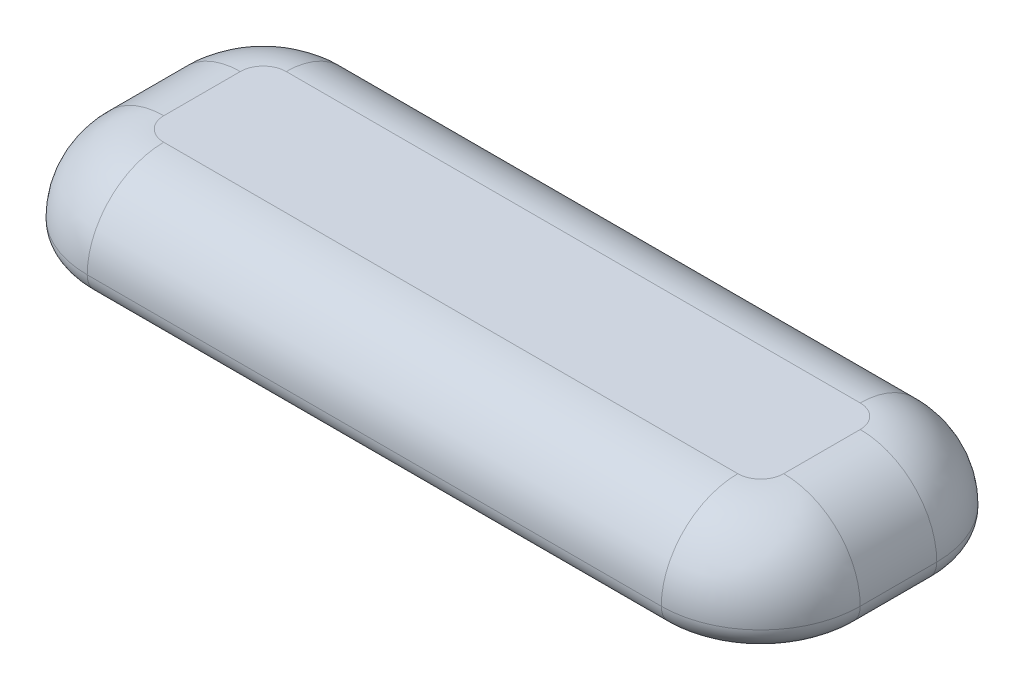
SolidWorks part; units mm, degrees
ref_plane "前视基准面" through (0, 0, 0) normal (0, 0, 1) x (1, 0, 0)
ref_plane "上视基准面" through (0, 0, 0) normal (0, 1, 0) x (1, 0, 0)
ref_plane "右视基准面" through (0, 0, 0) normal (1, 0, 0) x (0, 0, -1)
sketch "草图1" plane through (0, 0, 0) normal (0, 1, 0) x (1, 0, 0)
  line L1 (-37.5, 15) -> (37.5, 15)
  line L2 (-47.5, 5) -> (-47.5, -5)
  line L3 (-37.5, -15) -> (37.5, -15)
  line L4 (47.5, 5) -> (47.5, -5)
  line L5 (0, -15) -> (0, 15) construction
  line L6 (-47.5, 0) -> (47.5, 0) construction
  arc A0 (-47.5, -5) -> (-37.5, -15) centre (-37.5, -5) ccw
  arc A1 (-47.5, 5) -> (-37.5, 15) centre (-37.5, 5) cw
  arc A2 (37.5, 15) -> (47.5, 5) centre (37.5, 5) cw
  arc A3 (47.5, -5) -> (37.5, -15) centre (37.5, -5) cw
  point P0 (0, 0)
  point P8 (-47.5, 15)
  point P11 (47.5, 15)
  point P15 (47.5, -15)
  dimension "D3" = 10
  dimension "D1" = 95
  dimension "D2" = 30
extrude "凸台-拉伸1" add sketch "草图1" along normal blind 10
shell "抽壳2" thickness 3 removed face at (0, 0, 0) outward yes
fillet "圆角3" radius 10 8 edges at (46.6924, 13, -14.1924) (50.5, 13, 0) (46.6924, 13, 14.1924) (0, 13, 18) (-46.6924, 13, 14.1924) (-50.5, 13, 0) (-46.6924, 13, -14.1924) (0, 13, -18)
fillet "圆角4" radius 3 8 edges at (50.5, 0, 0) (46.6924, 0, 14.1924) (0, 0, 18) (-46.6924, 0, 14.1924) (-50.5, 0, 0) (-46.6924, 0, -14.1924) (0, 0, -18) (46.6924, 0, -14.1924)
ref_plane "基准面1" through (0, 10, 0) normal (0, -1, 0) x (-1, 0, 0)
sketch "草图2" plane through (0, 10, 0) normal (0, -1, 0) x (-1, 0, 0)
  line L0 (0, 0) -> (36.7, 0) construction
  line L1 (0, 0) -> (0, 6.5357) construction
  line L2 (34.625, 0.575) -> (38.775, 0.575)
  line L3 (34.625, 0.575) -> (34.625, -0.575)
  line L4 (34.625, -0.575) -> (38.775, -0.575)
  line L5 (38.775, 0.575) -> (38.775, -0.575)
  line L6 (36.7, -0.575) -> (36.7, 0.575) construction
  line L7 (34.625, 0) -> (38.775, 0) construction
  line L8 (36.125, 2.075) -> (37.275, 2.075)
  line L9 (36.125, 2.075) -> (36.125, -2.075)
  line L10 (36.125, -2.075) -> (37.275, -2.075)
  line L11 (37.275, 2.075) -> (37.275, -2.075)
  line L12 (36.7, -2.075) -> (36.7, 2.075) construction
  line L13 (36.125, 0) -> (37.275, 0) construction
  line L14 (-36.125, 0) -> (-37.275, 0) construction
  line L15 (-36.7, -2.075) -> (-36.7, 2.075) construction
  line L16 (-34.625, 0) -> (-38.775, 0) construction
  line L17 (-36.7, -0.575) -> (-36.7, 0.575) construction
  line L18 (-37.275, 2.075) -> (-37.275, -2.075)
  line L19 (-36.125, -2.075) -> (-37.275, -2.075)
  line L20 (-36.125, 2.075) -> (-36.125, -2.075)
  line L21 (-36.125, 2.075) -> (-37.275, 2.075)
  line L22 (-38.775, 0.575) -> (-38.775, -0.575)
  line L23 (-34.625, -0.575) -> (-38.775, -0.575)
  line L24 (-34.625, 0.575) -> (-34.625, -0.575)
  line L25 (-34.625, 0.575) -> (-38.775, 0.575)
  circle A0 centre (36.7, 0) radius 2.675
  circle A1 centre (-36.7, 0) radius 2.675
  dimension "D2" = 5.35
  dimension "D1" = 36.7
  dimension "D3" = 4.15
  dimension "D4" = 1.15
  dimension "D5" = 4.15
  dimension "D6" = 1.15
extrude "凸台-拉伸2" add sketch "草图2" along normal blind 8 contours A0 L8 L11 L2 L5 L4 L10 L9 L3 | A1 L25 L24 L23 L20 L19 L18 L22 L21 region at (-34.1007, 10, 0) region at (39.2993, 10, 0)
fillet "圆角7" radius 5 8 edges at (0, 10, 15) (44.5711, 10, 12.0711) (47.5, 10, 0) (44.5711, 10, -12.0711) (0, 10, -15) (-44.5711, 10, -12.0711) (-47.5, 10, 0) (-44.5711, 10, 12.0711)
chamfer "倒角1" distance 0.2 angle 45 12 edges at (36.7, 2, -2.075) (36.125, 2, -1.325) (35.375, 2, -0.575) (34.625, 2, 0) (35.375, 2, 0.575) (36.125, 2, 1.325) (36.7, 2, 2.075) (37.275, 2, 1.325) (38.025, 2, 0.575) (38.775, 2, 0) (38.025, 2, -0.575) (37.275, 2, -1.325)
chamfer "倒角2" distance 0.2 angle 45 12 edges at (-36.125, 2, -1.325) (-35.375, 2, -0.575) (-34.625, 2, 0) (-35.375, 2, 0.575) (-36.125, 2, 1.325) (-36.7, 2, 2.075) (-37.275, 2, 1.325) (-38.025, 2, 0.575) (-38.775, 2, 0) (-38.025, 2, -0.575) (-37.275, 2, -1.325) (-36.7, 2, -2.075)
fillet "圆角9" radius 5 1 edges at (36.7, 10, -2.675) second distance 5.5 conic rho 0.25 first distance on face at (36.7, 2, -2.675)
fillet "圆角10" radius 5 1 edges at (-36.7, 10, 2.675) second distance 5.5 conic rho 0.25 first distance on face at (-0.2762, 10, -1.25)
